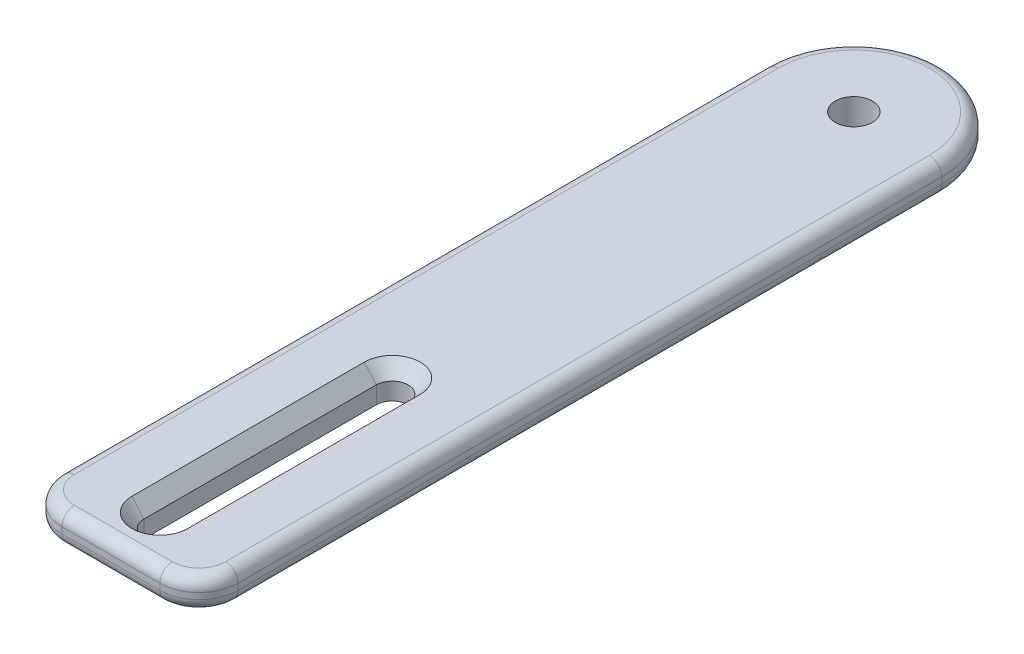
SolidWorks part; units mm, degrees
material "6061 Alloy"
ref_plane "Front Plane" through (0, 0, 0) normal (0, 0, 1) x (1, 0, 0)
ref_plane "Top Plane" through (0, 0, 0) normal (0, 1, 0) x (1, 0, 0)
ref_plane "Right Plane" through (0, 0, 0) normal (1, 0, 0) x (0, 0, -1)
sketch "Sketch1" plane through (0, 0, 0) normal (0, 1, 0) x (1, 0, 0)
  line L0 (9, 85) -> (9, 0) construction
  line L9 (0, 76) -> (0, 4)
  line L10 (4, 0) -> (14, 0)
  line L19 (18, 76) -> (18, 4)
  line L20 (6.1425, 28.78) -> (6.1425, 5)
  line L21 (7.368, 28.78) -> (7.368, 5)
  line L22 (11.8575, 28.78) -> (11.8575, 5)
  line L23 (10.6319, 28.78) -> (10.6319, 5)
  arc A0 (10.6319, 28.78) -> (7.368, 28.78) centre (9, 28.78) ccw
  arc A1 (7.368, 5) -> (10.6319, 5) centre (9, 5) ccw
  arc A2 (6.1425, 5) -> (11.8575, 5) centre (9, 5) ccw
  arc A3 (11.8575, 28.78) -> (6.1425, 28.78) centre (9, 28.78) ccw
  arc A4 (18, 76) -> (0, 76) centre (9, 76) ccw
  arc A5 (0, 4) -> (4, 0) centre (4, 4) ccw
  arc A6 (14, 0) -> (18, 4) centre (14, 4) ccw
  dimension "D5" = 3.2639
  dimension "D6" = 5.715
  dimension "D9" = 18
  dimension "D11" = 4
  dimension "D2" = 18
  dimension "D7" = 5
  dimension "D8" = 23.78
  dimension "D10" = 85
extrude "Link Base" add sketch "Sketch1" against normal blind 3.175 contours A4 L0 A3 L22 A2 L10 A6 L19 | L0 A4 L9 A5 L10 A2 L20 A3 | L0 A3 L20 A2 A1 L21 A0 | A3 L0 A0 L23 A1 A2 L22 region at (13.7942, 0, -44.7727) region at (4.2058, 0, -44.7727) region at (11.0663, 0, -16.89) region at (6.9337, 0, -16.89)
extrude "Contour for Flathead Screws" cut sketch "Sketch1<3>" against normal blind 10 draft 41 contours L22 A2 L20 A3
sketch "Sketch1<3>" plane through (0, 0, 0) normal (0, 1, 0) x (1, 0, 0) same geometry as "Sketch1"
hole_wizard "#6 Clearance Hole1" positions "Sketch3" profile "Sketch2" hole size "#6" standard "Ansi Inch" end condition through all
sketch "Sketch3" plane through (0, 0, 0) normal (0, 1, 0) x (-1, 0, 0)
  line L0 (-9, -85) -> (-9, -76) construction
  arc A0 (-18, -76) -> (0, -76) centre (-9, -76) ccw construction
  point P0 (-9, -76)
sketch "Sketch2" plane through (9, 0, -76) normal (1, 0, 0) x (0, 0, 1)
  line L0 (0, 0) -> (0, 3.175)
  line L1 (0, 3.175) -> (1.8986, 3.175)
  line L2 (1.8986, 3.175) -> (1.8986, 0)
  line L5 (1.8986, 0) -> (0, 0)
  line L11 (0, -6.35) -> (0, 107.95) construction
  dimension "Thru Hole Dia." = 3.7973
  dimension "Thru Hole Depth" = 3.175
fillet "Fillet1" radius 1.27 12 edges at (9, -3.175, -85) (0, -3.175, -40) (1.1716, -3.175, -1.1716) (9, -3.175, 0) (16.8284, -3.175, -1.1716) (9, 0, -85) (0, 0, -40) (1.1716, 0, -1.1716) (9, 0, 0) (16.8284, 0, -1.1716) (18, -3.175, -40) (18, 0, -40)
